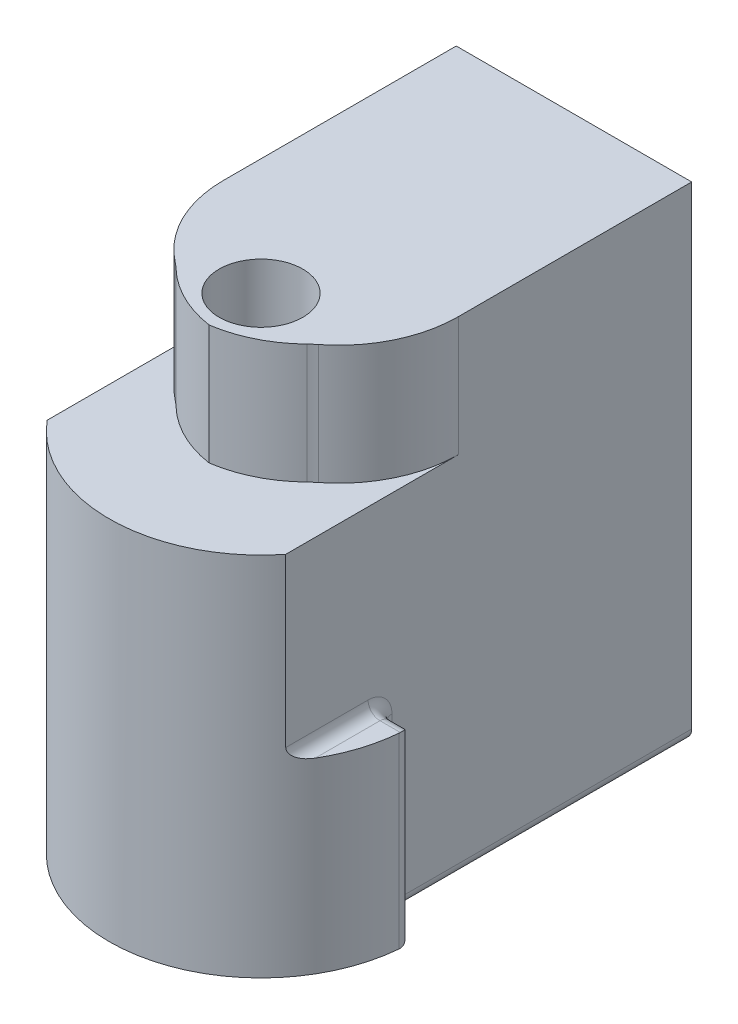
SolidWorks part; units mm, degrees
ref_plane "Front Plane" through (0, 0, 0) normal (0, 0, 1) x (1, 0, 0)
ref_plane "Top Plane" through (0, 0, 0) normal (0, 1, 0) x (1, 0, 0)
ref_plane "Right Plane" through (0, 0, 0) normal (1, 0, 0) x (0, 0, -1)
sketch "Sketch2" plane through (0, -2111.3899, 0) normal (0, 1, 0) x (1, 0, 0)
  circle A1 centre (-53.694, 163.8403) radius 12.7
extrude "Boss-Extrude6" add sketch "Sketch2" along normal blind 40.64
sketch "Sketch3" plane through (0, -2070.7499, 0) normal (0, 1, 0) x (1, 0, 0)
  circle A0 centre (-53.694, 163.8403) radius 3.5
  dimension "D1" = 7
extrude "Cut-Extrude1" cut sketch "Sketch3" against normal up to surface (40.64 mm away) up to face at (-66.394, -2111.3899, -163.8403)
sketch "Sketch4" plane through (0, -2111.3899, 0) normal (0, -1, 0) x (1, 0, 0)
  circle A0 centre (-61.9429, -159.0778) radius 1.778
  circle A2 centre (-53.694, -173.3653) radius 1.778
  circle A3 centre (-45.4451, -159.0778) radius 1.778
extrude "Cut-Extrude2" cut sketch "Sketch4" against normal blind 6
sketch "Sketch7" plane through (0, -2111.3899, 0) normal (0, -1, 0) x (1, 0, 0)
  line L9 (-40.994, -163.8403) -> (-40.994, -182.6343)
  line L10 (-40.994, -182.6343) -> (-66.1797, -182.6343)
  line L11 (-66.1797, -166.1636) -> (-66.1797, -182.6343)
  circle A0 centre (-53.694, -163.8403) radius 12.7 construction
  arc A1 (-66.1797, -166.1636) -> (-40.994, -163.8403) centre (-53.694, -163.8403) ccw
extrude "Boss-Extrude8" add sketch "Sketch7" against normal blind 10
sketch "Sketch8" plane through (0, 0, -182.6343) normal (0, 0, -1) x (-1, 0, 0)
  line L0 (40.994, -2101.3899) -> (40.994, -2111.3899) construction
  line L1 (40.994, -2101.3899) -> (66.1797, -2101.3899)
  line L2 (40.994, -2101.3899) -> (40.994, -2111.3899)
  line L3 (40.994, -2111.3899) -> (66.1797, -2111.3899)
  line L4 (66.1797, -2101.3899) -> (66.1797, -2111.3899)
  line L5 (66.1797, -2101.3899) -> (40.994, -2101.3899) construction
  line L6 (66.1797, -2111.3899) -> (40.994, -2111.3899) construction
  line L7 (66.1797, -2101.3899) -> (66.1797, -2111.3899) construction
extrude "Boss-Extrude9" add sketch "Sketch8" along normal up to surface (7.2848 mm away)
sketch "Sketch9" plane through (0, -2070.7499, 0) normal (0, 1, 0) x (1, 0, 0)
  line L0 (-40.994, 189.9191) -> (-40.994, 163.8403) construction
  line L2 (-66.1797, 163.8403) -> (-66.1797, 189.9191)
  line L3 (-66.1797, 189.9191) -> (-40.994, 189.9191)
  line L4 (-40.994, 163.8403) -> (-40.994, 189.9191)
  line L5 (-66.1797, 166.1636) -> (-66.1797, 189.9191) construction
  arc A0 (-40.994, 163.8403) -> (-66.1797, 163.8403) centre (-53.5868, 163.8403) ccw
extrude "Boss-Extrude10" add sketch "Sketch9" against normal up to surface (30.64 mm away) up to face at (-53.322, -2101.3899, -180.3317)
hole_wizard "CSK for M3 Flat Head Machine Screw1" positions "Sketch14" profile "Sketch15" countersink size "M3" standard "ANSI Metric"
sketch "Sketch14" plane through (0, 0, -189.9191) normal (0, 0, -1) x (-1, 0, 0)
  point P10 (53.5868, -2075.7499)
  point P12 (62.6264, -2075.7499)
  point P14 (44.5473, -2075.7499)
sketch "Sketch15" plane through (-53.5868, -2075.7499, -189.9191) normal (1, 0, 0) x (0, 1, 0)
  line L0 (0, 0) -> (0, 10)
  line L1 (0, 10) -> (1.7, 8.9785)
  line L2 (1.7, 8.9785) -> (1.7, 1.45)
  line L3 (1.7, 1.45) -> (3.15, 0)
  line L5 (3.15, 0) -> (0, 0)
  line L6 (-1.7, 1.45) -> (-3.15, 0) construction
  line L10 (0, 10) -> (-1.7, 8.9785) construction
  line L11 (0, -6.35) -> (0, 107.95) construction
  dimension "Hole Dia." = 3.4
  dimension "Hole Depth" = 10
  dimension "Near C'Sink Dia." = 6.3
  dimension "Near C'Sink Angle" = 90
  dimension "Drill Angle" = 118
ref_plane "Plane1" through (0, -2091.0699, 0) normal (0, 1, 0) x (1, 0, 0)
mirror "Mirror1" about plane through (0, -2091.0699, 0) normal (0, 1, 0) of "CSK for M3 Flat Head Machine Screw1"
sketch "Sketch16" plane through (0, -2070.7499, 0) normal (0, 1, 0) x (1, 0, 0)
  line L0 (-53.694, 151.1403) -> (-53.694, 163.1403) construction
  line L1 (-53.694, 151.1403) -> (-61.6485, 151.1403) construction
  line L2 (-57.6712, 151.1403) -> (-57.6712, 176.4403) construction
  line L3 (-53.694, 163.1403) -> (-66.3747, 163.1403) construction
  line L5 (-67.2059, 176.4403) -> (-63.4359, 176.4403)
  line L6 (-67.2059, 176.4403) -> (-67.2059, 154.4394)
  line L7 (-67.2059, 154.4394) -> (-63.4359, 154.4394)
  line L8 (-63.4359, 176.4403) -> (-63.4359, 154.4394)
  line L9 (-40.994, 163.8403) -> (-40.994, 189.9191) construction
  line L11 (-53.5868, 189.9191) -> (-53.5868, 168.4351) construction
  line L12 (-40.994, 189.9191) -> (-66.1797, 189.9191) construction
  line L13 (-53.4797, 163.1403) -> (-40.799, 163.1403) construction
  line L18 (-39.9677, 154.4394) -> (-43.7377, 154.4394)
  line L19 (-39.9677, 176.4403) -> (-39.9677, 154.4394)
  line L20 (-39.9677, 176.4403) -> (-43.7377, 176.4403)
  line L21 (-43.7377, 176.4403) -> (-43.7377, 154.4394)
  arc A0 (-66.1797, 166.1636) -> (-40.994, 163.8403) centre (-53.694, 163.8403) ccw construction
  dimension "D1" = 1.0262
  dimension "D2" = 25.3
  dimension "D3" = 16.6773
  dimension "D4" = 2.7438
  dimension "D5" = 26.7787
extrude "Cut-Extrude3" cut sketch "Sketch16" against normal blind 25
sketch "Sketch17" plane through (-66.1797, 0, 0) normal (-1, 0, 0) x (0, 0, 1)
  line L1 (-176.4403, -2095.7499) -> (-166.1636, -2095.7499)
  line L2 (-176.4403, -2095.7499) -> (-176.4403, -2111.3899)
  line L3 (-176.4403, -2111.3899) -> (-166.1636, -2111.3899)
  line L4 (-166.1636, -2095.7499) -> (-166.1636, -2111.3899)
extrude "Cut-Extrude4" cut sketch "Sketch17" against normal up to surface (2.7438 mm away) up to face at (-63.4359, -2083.2499, -166.0665)
sketch "Sketch18" plane through (-40.994, 0, 0) normal (1, 0, 0) x (0, 0, -1)
  line L1 (176.4403, -2095.7499) -> (163.8403, -2095.7499)
  line L2 (176.4403, -2095.7499) -> (176.4403, -2111.3899)
  line L3 (176.4403, -2111.3899) -> (163.8403, -2111.3899)
  line L4 (163.8403, -2095.7499) -> (163.8403, -2111.3899)
extrude "Cut-Extrude5" cut sketch "Sketch18" against normal up to surface (2.7438 mm away) up to face at (-43.7377, -2083.2499, -166.1981)
sketch "Sketch20" plane through (0, -2070.7499, 0) normal (0, 1, 0) x (1, 0, 0)
  line L0 (-63.4359, 176.4403) -> (-66.1797, 176.4403) construction
  line L1 (-43.7377, 176.4403) -> (-40.994, 176.4403)
  line L2 (-43.7377, 176.4403) -> (-43.7377, 189.9191)
  line L3 (-43.7377, 189.9191) -> (-40.994, 189.9191)
  line L4 (-40.994, 176.4403) -> (-40.994, 189.9191)
  line L5 (-63.4359, 176.4403) -> (-66.1797, 176.4403)
  line L6 (-63.4359, 176.4403) -> (-63.4359, 189.9191)
  line L7 (-63.4359, 189.9191) -> (-66.1797, 189.9191)
  line L8 (-66.1797, 176.4403) -> (-66.1797, 189.9191)
extrude "Cut-Extrude7" cut sketch "Sketch20" against normal blind 25
sketch "Sketch21" plane through (0, 0, -189.9191) normal (0, 0, -1) x (-1, 0, 0)
  line L0 (63.4359, -2095.7499) -> (63.4359, -2078.7941) construction
  line L1 (43.7377, -2070.7499) -> (49.4792, -2070.7499)
  line L2 (43.7377, -2070.7499) -> (43.7377, -2082.4464)
  line L3 (43.7377, -2082.4464) -> (49.4792, -2082.4464)
  line L4 (63.4359, -2070.7499) -> (63.4359, -2082.4464)
  line L5 (57.4971, -2082.4464) -> (57.4971, -2070.7499)
  line L6 (49.4792, -2082.4464) -> (49.4792, -2070.7499)
  line L7 (57.4971, -2082.4464) -> (63.4359, -2082.4464)
  line L8 (57.4971, -2070.7499) -> (63.4359, -2070.7499)
  line L9 (43.7377, -2072.7057) -> (43.7377, -2070.7499) construction
  line L10 (43.7377, -2070.7499) -> (63.4359, -2070.7499) construction
  dimension "D1" = 5.7415
  dimension "D2" = 13.7594
  dimension "D3" = 11.6965
extrude "Boss-Extrude12" add sketch "Sketch21" against normal blind 15
sketch "Sketch22" plane through (0, -2070.7499, 0) normal (0, 1, 0) x (1, 0, 0)
  line L0 (-53.694, 159.2557) -> (-57.3241, 159.2557)
  line L1 (-63.4359, 155.6927) -> (-63.4359, 166.1636) construction
  line L2 (-53.694, 159.2557) -> (-49.75, 159.2557)
  line L3 (-43.7377, 163.8403) -> (-43.7377, 155.956) construction
  line L4 (-43.7377, 159.2557) -> (-43.7377, 155.956)
  line L5 (-63.4359, 159.2557) -> (-63.4359, 155.6927)
  line L6 (-57.194, 163.8403) -> (-63.4359, 163.8403) construction
  line L7 (-63.4359, 155.6927) -> (-63.4359, 189.9191) construction
  line L8 (-63.4359, 163.8403) -> (-63.4359, 159.2557)
  line L9 (-43.7377, 163.8403) -> (-43.7377, 159.2557)
  arc A0 (-58.2786, 163.8403) -> (-53.694, 159.2557) centre (-53.694, 163.8403) ccw
  arc A1 (-63.4359, 155.6927) -> (-43.7377, 155.956) centre (-53.694, 163.8403) ccw
  circle A2 centre (-53.694, 163.8403) radius 3.5 construction
  arc A3 (-57.3241, 159.2557) -> (-63.4359, 163.8403) centre (-63.4359, 157.4742) ccw
  arc A4 (-43.7377, 163.8403) -> (-49.75, 159.2557) centre (-43.7377, 157.6058) ccw
  line M6 (-63.4359, 189.9191) -> (-63.4359, 155.6927)
  arc M7 (-63.4359, 155.6927) -> (-43.7377, 155.956) centre (-53.694, 163.8403) ccw
  line M8 (-43.7377, 155.956) -> (-43.7377, 189.9191)
  dimension "D1" = 4.5846
extrude "Cut-Extrude8" cut sketch "Sketch22" against normal blind 10 contours A4 L2 L0 A3 M8 M6 M7 region at (-53.6343, -2070.7499, -157.0534)
fillet "Fillet1" radius 10 2 edges at (-49.75, -2075.7499, -159.2557) (-57.3241, -2075.7499, -159.2557)
fillet "Fillet5" radius 10 2 edges at (-63.4359, -2075.7499, -163.8403) (-43.7377, -2075.7499, -163.8403)
sketch "Sketch23" plane through (0, 0, -189.9191) normal (0, 0, -1) x (-1, 0, 0)
  line L1 (41.3294, -2102.395) -> (48.7144, -2102.395)
  line L2 (41.3294, -2102.395) -> (41.3294, -2109.9374)
  line L3 (41.3294, -2109.9374) -> (48.7144, -2109.9374)
  line L4 (48.7144, -2102.395) -> (48.7144, -2109.9374)
  line L5 (58.4058, -2102.395) -> (65.8805, -2102.395)
  line L6 (58.4058, -2102.395) -> (58.4058, -2109.7908)
  line L7 (58.4058, -2109.7908) -> (65.8805, -2109.7908)
  line L8 (65.8805, -2102.395) -> (65.8805, -2109.7908)
extrude "Boss-Extrude13" add sketch "Sketch23" against normal blind 10
sketch "Sketch24" plane through (0, -2095.7499, 0) normal (0, 1, 0) x (1, 0, 0)
  line L1 (-43.7377, 189.9191) -> (-40.994, 189.9191)
  line L2 (-43.7377, 189.9191) -> (-43.7377, 176.4403)
  line L3 (-43.7377, 176.4403) -> (-40.994, 176.4403)
  line L4 (-40.994, 189.9191) -> (-40.994, 176.4403)
  line L5 (-66.1797, 189.9191) -> (-63.4359, 189.9191)
  line L6 (-66.1797, 189.9191) -> (-66.1797, 176.4403)
  line L7 (-66.1797, 176.4403) -> (-63.4359, 176.4403)
  line L8 (-63.4359, 189.9191) -> (-63.4359, 176.4403)
extrude "Cut-Extrude9" cut sketch "Sketch24" against normal blind 20
fillet "Fillet13" radius 1 12 edges at (-63.4359, -2111.3899, -178.0413) (-63.4359, -2095.7499, -160.9281) (-43.7377, -2095.7499, -159.8981) (-43.7377, -2111.3899, -176.8797) (-63.4359, -2103.5699, -166.1636) (-64.8078, -2095.7499, -166.1636) (-66.1797, -2103.5699, -166.1636) (-64.8078, -2111.3899, -166.1636) (-43.7377, -2103.5699, -163.8403) (-42.3658, -2111.3899, -163.8403) (-40.994, -2103.5699, -163.8403) (-42.3658, -2095.7499, -163.8403)
